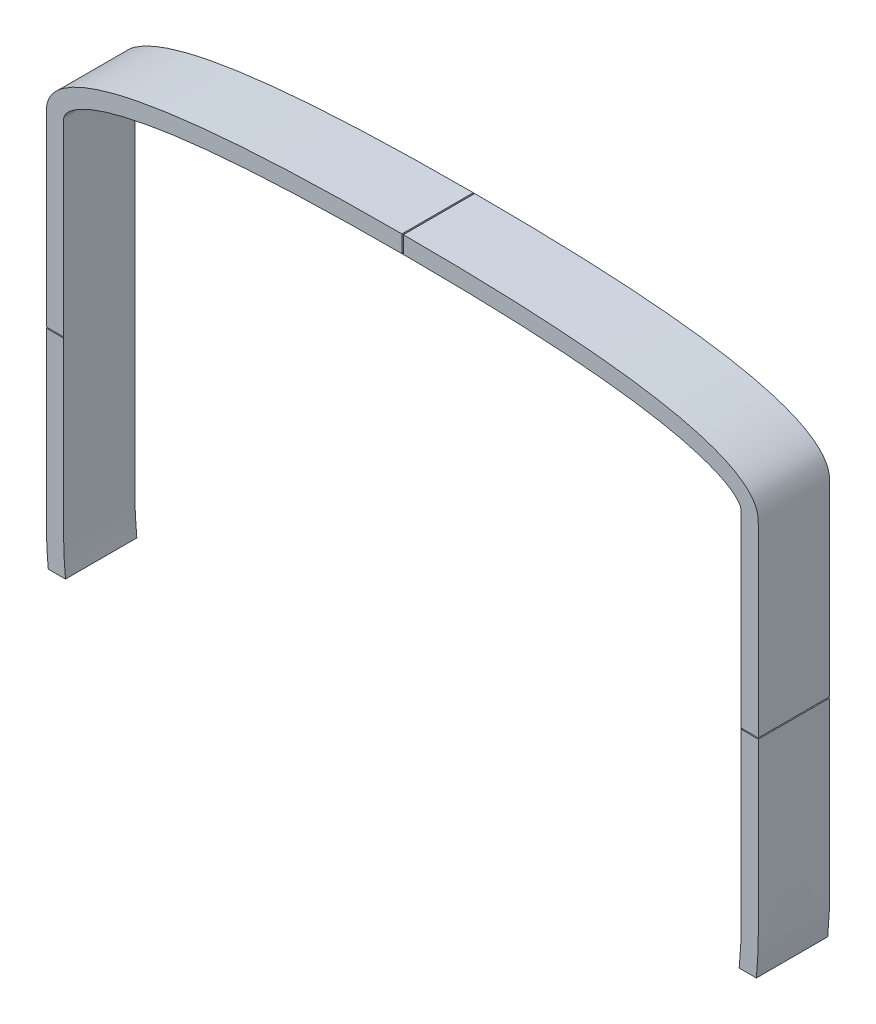
SolidWorks part; units mm, degrees
ref_plane "Front Plane" through (0, 0, 0) normal (0, 0, 1) x (1, 0, 0)
ref_plane "Top Plane" through (0, 0, 0) normal (0, 1, 0) x (1, 0, 0)
ref_plane "Right Plane" through (0, 0, 0) normal (1, 0, 0) x (0, 0, -1)
sketch "Sketch1" plane through (0, 0, 0) normal (0, 0, 1) x (1, 0, 0)
  line L0 (-100.01, 47.0605) -> (-95.145, 47.0605) construction
  line L1 (-95.145, 47.0605) -> (-95.145, 47.3605) construction
  line L2 (-95.145, 47.3605) -> (-100.01, 47.3605) construction
  line L3 (0.3, -80.0112) -> (0.3, -75.1462) construction
  line L4 (0.3, -75.1462) -> (-0.1, -75.1462) construction
  line L5 (-0.1, -75.1462) -> (-0.1, -80.0113) construction
  line L6 (100.01, 47.0605) -> (95.145, 47.0605) construction
  line L7 (95.145, 47.0605) -> (95.145, 47.3605) construction
  line L8 (95.145, 47.3605) -> (100.01, 47.3605) construction
  line L9 (-0.1, 120.0108) -> (-0.1, 115.1456) construction
  line L10 (-0.1, 115.1456) -> (0.3, 115.1456) construction
  line L11 (0.3, 115.1456) -> (0.3, 120) construction
  line L12 (-100.01, 47.0605) -> (-95.145, 47.0605)
  line L13 (-95.145, 47.0605) -> (-95.145, 47.3605)
  line L14 (-95.145, 47.3605) -> (-100.01, 47.3605)
  line L15 (0.3, -80.0112) -> (0.3, -75.1462)
  line L16 (0.3, -75.1462) -> (-0.1, -75.1462)
  line L17 (-0.1, -75.1462) -> (-0.1, -80.0113)
  line L18 (100.01, 47.0605) -> (95.145, 47.0605)
  line L19 (95.145, 47.0605) -> (95.145, 47.3605)
  line L20 (95.145, 47.3605) -> (100.01, 47.3605)
  line L21 (-0.1, 120.0108) -> (-0.1, 115.1456)
  line L22 (-0.1, 115.1456) -> (0.3, 115.1456)
  line L23 (0.3, 115.1456) -> (0.3, 120)
  spline S1 degree 3 poles (99.7997, 99.6773) (99.8036, 99.9509) (99.7918, 100.4046) (99.7567, 100.8662) (99.681, 101.3713) (99.4748, 102.3026) (98.9784, 103.5224) (98.2111, 104.7064) (97.4509, 105.6067) (96.7168, 106.336) (95.7397, 107.1776) (94.5505, 108.0336) (93.1451, 108.8913) (91.7553, 109.627) (90.3759, 110.2763) (88.5549, 111.0479) (86.2863, 111.8842) (83.5821, 112.7336) (80.8863, 113.4732) (77.3062, 114.3386) (72.8372, 115.247) (67.4911, 116.1276) (62.1537, 116.8577) (55.0502, 117.6648) (46.1798, 118.4308) (35.5554, 119.0568) (24.9443, 119.4728) (10.8109, 119.7907) (-3.2959, 119.8408) (-17.4186, 119.6586) (-28.0207, 119.3706) (-38.6348, 118.9) (-49.264, 118.1957) (-58.1353, 117.3502) (-65.2481, 116.4514) (-70.5879, 115.6377) (-75.9423, 114.6434) (-80.4143, 113.6143) (-84.0118, 112.6066) (-86.7154, 111.7373) (-88.9907, 110.8755) (-90.8116, 110.0789) (-92.1968, 109.4029) (-93.5848, 108.6377) (-94.773, 107.876) (-95.7176, 107.1784) (-96.45, 106.576) (-97.1862, 105.883) (-97.9288, 105.0629) (-98.5735, 104.1718) (-99.0633, 103.2704) (-99.3935, 102.4897) (-99.6149, 101.7198) (-99.7273, 101.0847) (-99.7694, 100.7104) (-99.7903, 100.4114) (-99.7992, 100.1667) (-99.8002, 99.9845) (-99.7998, 99.869) (-99.7998, 99.7406) (-99.7998, 99.5238) (-99.8, 99.2514) (-99.8003, 98.8108) (-99.8005, 98.2617) (-99.8006, 97.6024) (-99.8006, 96.7238) (-99.8004, 95.626) (-99.8, 94.3096) (-99.7998, 92.994) (-99.7998, 91.2393) (-99.8, 89.0456) (-99.8002, 86.4124) (-99.8002, 83.7794) (-99.8003, 80.2688) (-99.8002, 75.8805) (-99.8, 70.6147) (-99.7999, 65.349) (-99.7999, 60.0833) (-99.7999, 53.0623) (-99.8, 44.2861) (-99.8001, 33.7545) (-99.8005, 23.2232) (-99.7997, 14.4459) (-99.8011, 7.4266) (-99.7969, 3.0338) (-99.8053, -0.466) (-99.7591, -4.1567) (-99.4387, -10.5423) (-98.2942, -19.73) (-95.5017, -30.6179) (-91.0075, -41.0897) (-84.6521, -50.6636) (-76.6002, -58.8628) (-67.303, -65.4359) (-53.8961, -72.1154) (-36.165, -77.1506) (-18.1876, -79.2977) (-3.835, -79.8498) (10.4785, -79.7642) (28.4686, -78.3932) (49.8925, -73.7834) (67.0953, -66.0502) (79.0866, -56.6481) (86.6805, -48.0163) (92.5016, -38.1179) (96.4764, -27.4833) (98.4332, -18.3609) (99.3377, -11.0291) (99.6551, -6.4456) (99.7809, -2.7913) (99.8043, -0.0384) (99.7991, 2.5844) (99.8005, 6.0917) (99.7999, 10.4829) (99.8001, 17.5023) (99.8, 26.2794) (99.8, 36.8107) (99.8, 47.3423) (99.8, 56.1185) (99.8, 63.1396) (99.8, 68.4053) (99.8, 73.6711) (99.8, 78.9369) (99.8, 83.325) (99.8, 86.8355) (99.8, 89.4684) (99.8, 91.6625) (99.8, 93.4178) (99.8, 94.7342) (99.8, 95.8313) (99.8, 96.7088) (99.8, 97.3675) (99.8, 98.0238) (99.8, 98.5785) (99.8, 99.0062) (99.8001, 99.2955) (99.7997, 99.5144) (99.7997, 99.6773) (99.8036, 99.9509) (99.7918, 100.4046) knots -0.000977 -0.000732 -0.000488 0 0.000244 0.000488 0.000732 0.000977 0.001953 0.00293 0.003906 0.004883 0.005859 0.007812 0.009766 0.011719 0.013672 0.015625 0.019531 0.023438 0.027344 0.03125 0.039062 0.046875 0.054688 0.0625 0.078125 0.09375 0.109375 0.125 0.15625 0.171875 0.1875 0.203125 0.21875 0.234375 0.242188 0.25 0.257812 0.265625 0.269531 0.273438 0.277344 0.279297 0.28125 0.283203 0.285156 0.286133 0.287109 0.288086 0.289062 0.290039 0.290527 0.291016 0.291504 0.291748 0.291992 0.292114 0.292236 0.292358 0.29248 0.292725 0.292969 0.293457 0.293945 0.294922 0.295898 0.296875 0.298828 0.300781 0.302734 0.304688 0.308594 0.3125 0.316406 0.320312 0.328125 0.335938 0.34375 0.351562 0.359375 0.375 0.390625 0.40625 0.421875 0.429688 0.4375 0.441406 0.445312 0.453125 0.46875 0.484375 0.5 0.515625 0.53125 0.546875 0.5625 0.59375 0.625 0.640625 0.65625 0.6875 0.71875 0.75 0.765625 0.78125 0.796875 0.8125 0.828125 0.835938 0.84375 0.847656 0.851562 0.855469 0.859375 0.867188 0.875 0.890625 0.90625 0.921875 0.9375 0.945312 0.953125 0.960938 0.96875 0.976562 0.980469 0.984375 0.988281 0.990234 0.992188 0.994141 0.995117 0.996094 0.99707 0.998047 0.998535 0.999023 0.999268 0.999512 1 1.000244 1.000488 1.000732 only from (99.7993, 100.0793) to (99.7993, 100.0793)
  spline S2 degree 3 poles (99.7997, 99.6773) (99.8036, 99.9509) (99.7918, 100.4046) (99.7567, 100.8662) (99.681, 101.3713) (99.4748, 102.3026) (98.9784, 103.5224) (98.2111, 104.7064) (97.4509, 105.6067) (96.7168, 106.336) (95.7397, 107.1776) (94.5505, 108.0336) (93.1451, 108.8913) (91.7553, 109.627) (90.3759, 110.2763) (88.5549, 111.0479) (86.2863, 111.8842) (83.5821, 112.7336) (80.8863, 113.4732) (77.3062, 114.3386) (72.8372, 115.247) (67.4911, 116.1276) (62.1537, 116.8577) (55.0502, 117.6648) (46.1798, 118.4308) (35.5554, 119.0568) (24.9443, 119.4728) (10.8109, 119.7907) (-3.2959, 119.8408) (-17.4186, 119.6586) (-28.0207, 119.3706) (-38.6348, 118.9) (-49.264, 118.1957) (-58.1353, 117.3502) (-65.2481, 116.4514) (-70.5879, 115.6377) (-75.9423, 114.6434) (-80.4143, 113.6143) (-84.0118, 112.6066) (-86.7154, 111.7373) (-88.9907, 110.8755) (-90.8116, 110.0789) (-92.1968, 109.4029) (-93.5848, 108.6377) (-94.773, 107.876) (-95.7176, 107.1784) (-96.45, 106.576) (-97.1862, 105.883) (-97.9288, 105.0629) (-98.5735, 104.1718) (-99.0633, 103.2704) (-99.3935, 102.4897) (-99.6149, 101.7198) (-99.7273, 101.0847) (-99.7694, 100.7104) (-99.7903, 100.4114) (-99.7992, 100.1667) (-99.8002, 99.9845) (-99.7998, 99.869) (-99.7998, 99.7406) (-99.7998, 99.5238) (-99.8, 99.2514) (-99.8003, 98.8108) (-99.8005, 98.2617) (-99.8006, 97.6024) (-99.8006, 96.7238) (-99.8004, 95.626) (-99.8, 94.3096) (-99.7998, 92.994) (-99.7998, 91.2393) (-99.8, 89.0456) (-99.8002, 86.4124) (-99.8002, 83.7794) (-99.8003, 80.2688) (-99.8002, 75.8805) (-99.8, 70.6147) (-99.7999, 65.349) (-99.7999, 60.0833) (-99.7999, 53.0623) (-99.8, 44.2861) (-99.8001, 33.7545) (-99.8005, 23.2232) (-99.7997, 14.4459) (-99.8011, 7.4266) (-99.7969, 3.0338) (-99.8053, -0.466) (-99.7591, -4.1567) (-99.4387, -10.5423) (-98.2942, -19.73) (-95.5017, -30.6179) (-91.0075, -41.0897) (-84.6521, -50.6636) (-76.6002, -58.8628) (-67.303, -65.4359) (-53.8961, -72.1154) (-36.165, -77.1506) (-18.1876, -79.2977) (-3.835, -79.8498) (10.4785, -79.7642) (28.4686, -78.3932) (49.8925, -73.7834) (67.0953, -66.0502) (79.0866, -56.6481) (86.6805, -48.0163) (92.5016, -38.1179) (96.4764, -27.4833) (98.4332, -18.3609) (99.3377, -11.0291) (99.6551, -6.4456) (99.7809, -2.7913) (99.8043, -0.0384) (99.7991, 2.5844) (99.8005, 6.0917) (99.7999, 10.4829) (99.8001, 17.5023) (99.8, 26.2794) (99.8, 36.8107) (99.8, 47.3423) (99.8, 56.1185) (99.8, 63.1396) (99.8, 68.4053) (99.8, 73.6711) (99.8, 78.9369) (99.8, 83.325) (99.8, 86.8355) (99.8, 89.4684) (99.8, 91.6625) (99.8, 93.4178) (99.8, 94.7342) (99.8, 95.8313) (99.8, 96.7088) (99.8, 97.3675) (99.8, 98.0238) (99.8, 98.5785) (99.8, 99.0062) (99.8001, 99.2955) (99.7997, 99.5144) (99.7997, 99.6773) (99.8036, 99.9509) (99.7918, 100.4046) knots -0.000977 -0.000732 -0.000488 0 0.000244 0.000488 0.000732 0.000977 0.001953 0.00293 0.003906 0.004883 0.005859 0.007812 0.009766 0.011719 0.013672 0.015625 0.019531 0.023438 0.027344 0.03125 0.039062 0.046875 0.054688 0.0625 0.078125 0.09375 0.109375 0.125 0.15625 0.171875 0.1875 0.203125 0.21875 0.234375 0.242188 0.25 0.257812 0.265625 0.269531 0.273438 0.277344 0.279297 0.28125 0.283203 0.285156 0.286133 0.287109 0.288086 0.289062 0.290039 0.290527 0.291016 0.291504 0.291748 0.291992 0.292114 0.292236 0.292358 0.29248 0.292725 0.292969 0.293457 0.293945 0.294922 0.295898 0.296875 0.298828 0.300781 0.302734 0.304688 0.308594 0.3125 0.316406 0.320312 0.328125 0.335938 0.34375 0.351562 0.359375 0.375 0.390625 0.40625 0.421875 0.429688 0.4375 0.441406 0.445312 0.453125 0.46875 0.484375 0.5 0.515625 0.53125 0.546875 0.5625 0.59375 0.625 0.640625 0.65625 0.6875 0.71875 0.75 0.765625 0.78125 0.796875 0.8125 0.828125 0.835938 0.84375 0.847656 0.851562 0.855469 0.859375 0.867188 0.875 0.890625 0.90625 0.921875 0.9375 0.945312 0.953125 0.960938 0.96875 0.976562 0.980469 0.984375 0.988281 0.990234 0.992188 0.994141 0.995117 0.996094 0.99707 0.998047 0.998535 0.999023 0.999268 0.999512 1 1.000244 1.000488 1.000732 only from (99.7993, 100.0793) to (99.7993, 100.0793)
  spline S3 degree 3 poles (94.9991, 99.6498) (95.0033, 99.9945) (94.9886, 100.3305) (94.9285, 100.6507) (94.8294, 100.9604) (94.5623, 101.5544) (93.9794, 102.3192) (93.0263, 103.2069) (91.6762, 104.1962) (89.7643, 105.2891) (86.7225, 106.6551) (82.5543, 108.083) (76.1132, 109.7535) (67.4455, 111.3546) (54.2601, 113.0179) (36.6733, 114.3033) (21.0967, 114.796) (10.1079, 114.9512) (4.9035, 114.9925) (-0.3225, 115.0048) (-7.3652, 114.9836) (-16.0311, 114.8829) (-26.9636, 114.6065) (-37.956, 114.1366) (-48.8577, 113.4115) (-58.667, 112.4743) (-66.6295, 111.4261) (-72.9317, 110.3437) (-78.1678, 109.2363) (-83.1304, 107.9121) (-87.3123, 106.426) (-90.3426, 104.9929) (-92.2115, 103.8445) (-93.3583, 102.913) (-93.9767, 102.2848) (-94.5313, 101.602) (-94.8966, 100.9077) (-94.9869, 100.3092) (-95.0003, 100.0907) (-94.9996, 99.7607) (-95.0013, 97.7241) (-94.9995, 93.9804) (-95.0006, 84.2276) (-94.9997, 68.373) (-95, 40.1872) (-95.0005, 17.4761) (-94.9999, 2.1967) (-95.0002, 0.4352) (-94.9982, -2.3323) (-94.8101, -8.1993) (-93.8713, -17.1447) (-91.4322, -27.5753) (-87.8502, -36.4563) (-83.6838, -43.555) (-79.3185, -49.2124) (-73.5088, -55.0355) (-65.8142, -60.7188) (-56.8099, -65.3701) (-47.6395, -68.7951) (-37.8771, -71.4534) (-26.8877, -73.4301) (-15.4181, -74.5813) (-6.1485, -74.9679) (0.8919, -75.0173) (7.9604, -74.9151) (16.7848, -74.4683) (27.3133, -73.3359) (37.741, -71.4746) (51.3819, -67.8285) (64.4819, -61.969) (74.2954, -54.3104) (79.226, -49.2152) (83.6031, -43.7463) (88.1341, -36.0845) (91.8283, -26.2136) (94.0819, -15.7449) (94.8156, -7.8256) (94.9715, -2.8766) (94.9968, -1.1263) (95.0018, 0.6243) (94.9994, 2.8316) (95.0003, 6.3331) (94.9999, 10.7101) (95, 14.3284) (95, 16.3126) (95, 16.6627) (95, 17.0129) (95, 17.3631) (95, 17.7132) (95, 18.0634) (95, 18.4135) (95, 18.7637) (95, 19.1138) (95, 19.464) (95, 19.8142) (95, 20.1643) (95, 20.5145) (95, 20.8646) (95, 21.2148) (95, 21.5649) (95, 21.9151) (95, 22.2652) (95, 22.6154) (95, 22.9656) (95, 23.3157) (95, 23.6659) (95, 24.016) (95, 24.3662) (95, 24.7163) (95, 25.0665) (95, 25.4167) (95, 25.7668) (95, 26.117) (95, 26.4671) (95, 26.8173) (95, 27.1674) (95, 27.5176) (95, 27.8678) (95, 28.2179) (95, 28.5681) (95, 28.9182) (95, 29.2684) (95, 29.6185) (95, 29.9687) (95, 30.3188) (95, 30.669) (95, 31.0192) (95, 31.3693) (95, 31.7195) (95, 32.0696) (95, 32.4198) (95, 32.7699) (95, 33.1201) (95, 33.4703) (95, 33.8204) (95, 34.1706) (95, 34.5207) (95, 34.8709) (95, 35.221) (95, 35.5712) (95, 35.9213) (95, 36.2715) (95, 36.6217) (95, 36.9718) (95, 37.322) (95, 37.6721) (95, 38.0223) (95, 38.3724) (95, 38.7226) (95, 39.0728) (95, 39.4229) (95, 39.7731) (95, 40.1232) (95, 40.4734) (95, 40.8235) (95, 41.1737) (95, 41.5239) (95, 41.874) (95, 42.2242) (95, 42.5743) (95, 42.9245) (95, 43.2746) (95, 43.6248) (95, 43.9749) (95, 44.3251) (95, 44.6753) (95, 45.0254) (95, 45.3756) (95, 45.7257) (95, 46.0759) (95, 46.426) (95, 46.7762) (95, 47.1264) (95, 47.4765) (95, 47.8267) (95, 48.1768) (95, 48.527) (95, 48.8771) (95, 49.2273) (95, 49.5774) (95, 49.9276) (95, 50.2778) (95, 50.6279) (95, 50.9781) (95, 51.3282) (95, 51.6784) (95, 52.0285) (95, 52.3787) (95, 52.7289) (95, 53.079) (95, 53.4292) (95, 53.7793) (95, 54.1295) (95, 54.4796) (95, 54.8298) (95, 55.18) (95, 55.5301) (95, 55.8803) (95, 56.2304) (95, 56.5806) (95, 56.9307) (95, 57.2809) (95, 57.631) (95, 57.9812) (95, 58.3314) (95, 58.6815) (95, 59.0317) (95, 59.3818) (95, 59.732) (95, 60.0821) (95, 60.4323) (95, 60.7825) (95, 61.1326) (95, 61.4828) (95, 61.8329) (95, 62.1831) (95, 62.5332) (95, 62.8834) (95, 63.2336) (95, 63.5837) (95, 63.9339) (95, 64.284) (95, 64.6342) (95, 64.9843) (95, 65.3345) (95, 65.6846) (95, 66.0348) (95, 66.385) (95, 66.7351) (95, 67.0853) (95, 67.4354) (95, 67.7856) (95, 68.1357) (95, 68.4859) (95, 68.8361) (95, 69.1862) (95, 69.5364) (95, 69.8865) (95, 70.2367) (95, 70.5868) (95, 70.937) (95, 71.2871) (95, 71.6373) (95, 71.9875) (95, 72.3376) (95, 72.6878) (95, 73.0379) (95, 73.3881) (95, 73.7382) (95, 74.0884) (95, 74.4386) (95, 74.7887) (95, 75.1389) (95, 75.489) (95, 75.8392) (95, 76.1893) (95, 76.5395) (95, 76.8897) (95, 77.2398) (95, 77.59) (95, 77.9401) (95, 78.2903) (95, 78.6404) (95, 78.9906) (95, 79.3407) (95, 79.6909) (95, 80.0411) (95, 80.3912) (95, 80.7414) (95, 81.0915) (95, 81.4417) (95, 81.7918) (95, 82.142) (95, 82.4922) (95, 82.8423) (95, 83.1925) (95, 83.5426) (95, 83.8928) (95, 84.2429) (95, 84.5931) (95, 84.9432) (95, 85.2934) (95, 85.6436) (95, 85.9937) (95, 86.3439) (95, 86.694) (95, 87.0442) (95, 87.3943) (95, 87.7445) (95, 88.0947) (95, 88.4448) (95, 88.795) (95, 89.1451) (95, 89.4953) (95, 89.8454) (95, 90.1956) (95, 90.5458) (95, 90.8959) (95, 91.2461) (95, 91.5962) (95, 91.9464) (95, 92.2965) (95, 92.6467) (95, 92.9968) (95, 93.347) (95, 93.6972) (95, 94.0473) (95, 94.3975) (95, 94.7476) (95, 95.0978) (95, 95.4479) (95, 95.7981) (95, 96.1483) (95, 96.4984) (95, 96.8486) (95, 97.1987) (95, 97.5489) (95, 97.899) (95, 98.2492) (95, 98.5994) (94.9999, 98.9495) (95.0002, 99.2997) (94.9991, 99.6498) (95.0033, 99.9945) (94.9886, 100.3305) knots -0.001559 -0.001039 -0.00052 0 0.000495 0.000974 0.001446 0.001939 0.003867 0.005664 0.00773 0.011301 0.015445 0.022555 0.030881 0.045044 0.061752 0.090013 0.123492 0.131103 0.138928 0.146657 0.154364 0.170275 0.185229 0.203037 0.219242 0.233854 0.246889 0.254977 0.26231 0.270704 0.277822 0.282028 0.285605 0.287554 0.288589 0.28952 0.291476 0.291962 0.292206 0.29245 0.293431 0.301271 0.309112 0.33684 0.371839 0.434565 0.437925 0.439846 0.442406 0.450243 0.465965 0.482358 0.497762 0.508388 0.518904 0.52948 0.544908 0.56127 0.574423 0.588416 0.606248 0.624055 0.639683 0.647525 0.655389 0.671146 0.686832 0.702495 0.718232 0.749659 0.765474 0.773344 0.781173 0.796611 0.812727 0.82787 0.84415 0.848045 0.849909 0.851941 0.855837 0.859734 0.867526 0.875319 0.875838 0.876358 0.876877 0.877397 0.877916 0.878436 0.878955 0.879475 0.879994 0.880514 0.881033 0.881553 0.882072 0.882592 0.883111 0.883631 0.88415 0.88467 0.885189 0.885709 0.886228 0.886748 0.887267 0.887787 0.888306 0.888826 0.889345 0.889865 0.890384 0.890904 0.891423 0.891943 0.892462 0.892982 0.893501 0.894021 0.89454 0.89506 0.895579 0.896099 0.896618 0.897138 0.897657 0.898177 0.898696 0.899216 0.899735 0.900255 0.900774 0.901294 0.901813 0.902333 0.902852 0.903372 0.903891 0.904411 0.90493 0.90545 0.90597 0.906489 0.907009 0.907528 0.908048 0.908567 0.909087 0.909606 0.910126 0.910645 0.911165 0.911684 0.912204 0.912723 0.913243 0.913762 0.914282 0.914801 0.915321 0.91584 0.91636 0.916879 0.917399 0.917918 0.918438 0.918957 0.919477 0.919996 0.920516 0.921035 0.921555 0.922074 0.922594 0.923113 0.923633 0.924152 0.924672 0.925191 0.925711 0.92623 0.92675 0.927269 0.927789 0.928308 0.928828 0.929347 0.929867 0.930386 0.930906 0.931425 0.931945 0.932464 0.932984 0.933503 0.934023 0.934542 0.935062 0.935581 0.936101 0.93662 0.93714 0.937659 0.938179 0.938698 0.939218 0.939737 0.940257 0.940776 0.941296 0.941815 0.942335 0.942854 0.943374 0.943893 0.944413 0.944932 0.945452 0.945971 0.946491 0.94701 0.94753 0.948049 0.948569 0.949088 0.949608 0.950127 0.950647 0.951166 0.951686 0.952205 0.952725 0.953245 0.953764 0.954284 0.954803 0.955323 0.955842 0.956362 0.956881 0.957401 0.95792 0.95844 0.958959 0.959479 0.959998 0.960518 0.961037 0.961557 0.962076 0.962596 0.963115 0.963635 0.964154 0.964674 0.965193 0.965713 0.966232 0.966752 0.967271 0.967791 0.96831 0.96883 0.969349 0.969869 0.970388 0.970908 0.971427 0.971947 0.972466 0.972986 0.973505 0.974025 0.974544 0.975064 0.975583 0.976103 0.976622 0.977142 0.977661 0.978181 0.9787 0.97922 0.979739 0.980259 0.980778 0.981298 0.981817 0.982337 0.982856 0.983376 0.983895 0.984415 0.984934 0.985454 0.985973 0.986493 0.987012 0.987532 0.988051 0.988571 0.98909 0.98961 0.990129 0.990649 0.991168 0.991688 0.992207 0.992727 0.993246 0.993766 0.994285 0.994805 0.995324 0.995844 0.996363 0.996883 0.997402 0.997922 0.998441 0.998961 0.99948 1 1.000495 1.000974 1.001446 only from (95, 100) to (95, 100)
  spline S4 degree 3 poles (94.9991, 99.6498) (95.0033, 99.9945) (94.9886, 100.3305) (94.9285, 100.6507) (94.8294, 100.9604) (94.5623, 101.5544) (93.9794, 102.3192) (93.0263, 103.2069) (91.6762, 104.1962) (89.7643, 105.2891) (86.7225, 106.6551) (82.5543, 108.083) (76.1132, 109.7535) (67.4455, 111.3546) (54.2601, 113.0179) (36.6733, 114.3033) (21.0967, 114.796) (10.1079, 114.9512) (4.9035, 114.9925) (-0.3225, 115.0048) (-7.3652, 114.9836) (-16.0311, 114.8829) (-26.9636, 114.6065) (-37.956, 114.1366) (-48.8577, 113.4115) (-58.667, 112.4743) (-66.6295, 111.4261) (-72.9317, 110.3437) (-78.1678, 109.2363) (-83.1304, 107.9121) (-87.3123, 106.426) (-90.3426, 104.9929) (-92.2115, 103.8445) (-93.3583, 102.913) (-93.9767, 102.2848) (-94.5313, 101.602) (-94.8966, 100.9077) (-94.9869, 100.3092) (-95.0003, 100.0907) (-94.9996, 99.7607) (-95.0013, 97.7241) (-94.9995, 93.9804) (-95.0006, 84.2276) (-94.9997, 68.373) (-95, 40.1872) (-95.0005, 17.4761) (-94.9999, 2.1967) (-95.0002, 0.4352) (-94.9982, -2.3323) (-94.8101, -8.1993) (-93.8713, -17.1447) (-91.4322, -27.5753) (-87.8502, -36.4563) (-83.6838, -43.555) (-79.3185, -49.2124) (-73.5088, -55.0355) (-65.8142, -60.7188) (-56.8099, -65.3701) (-47.6395, -68.7951) (-37.8771, -71.4534) (-26.8877, -73.4301) (-15.4181, -74.5813) (-6.1485, -74.9679) (0.8919, -75.0173) (7.9604, -74.9151) (16.7848, -74.4683) (27.3133, -73.3359) (37.741, -71.4746) (51.3819, -67.8285) (64.4819, -61.969) (74.2954, -54.3104) (79.226, -49.2152) (83.6031, -43.7463) (88.1341, -36.0845) (91.8283, -26.2136) (94.0819, -15.7449) (94.8156, -7.8256) (94.9715, -2.8766) (94.9968, -1.1263) (95.0018, 0.6243) (94.9994, 2.8316) (95.0003, 6.3331) (94.9999, 10.7101) (95, 14.3284) (95, 16.3126) (95, 16.6627) (95, 17.0129) (95, 17.3631) (95, 17.7132) (95, 18.0634) (95, 18.4135) (95, 18.7637) (95, 19.1138) (95, 19.464) (95, 19.8142) (95, 20.1643) (95, 20.5145) (95, 20.8646) (95, 21.2148) (95, 21.5649) (95, 21.9151) (95, 22.2652) (95, 22.6154) (95, 22.9656) (95, 23.3157) (95, 23.6659) (95, 24.016) (95, 24.3662) (95, 24.7163) (95, 25.0665) (95, 25.4167) (95, 25.7668) (95, 26.117) (95, 26.4671) (95, 26.8173) (95, 27.1674) (95, 27.5176) (95, 27.8678) (95, 28.2179) (95, 28.5681) (95, 28.9182) (95, 29.2684) (95, 29.6185) (95, 29.9687) (95, 30.3188) (95, 30.669) (95, 31.0192) (95, 31.3693) (95, 31.7195) (95, 32.0696) (95, 32.4198) (95, 32.7699) (95, 33.1201) (95, 33.4703) (95, 33.8204) (95, 34.1706) (95, 34.5207) (95, 34.8709) (95, 35.221) (95, 35.5712) (95, 35.9213) (95, 36.2715) (95, 36.6217) (95, 36.9718) (95, 37.322) (95, 37.6721) (95, 38.0223) (95, 38.3724) (95, 38.7226) (95, 39.0728) (95, 39.4229) (95, 39.7731) (95, 40.1232) (95, 40.4734) (95, 40.8235) (95, 41.1737) (95, 41.5239) (95, 41.874) (95, 42.2242) (95, 42.5743) (95, 42.9245) (95, 43.2746) (95, 43.6248) (95, 43.9749) (95, 44.3251) (95, 44.6753) (95, 45.0254) (95, 45.3756) (95, 45.7257) (95, 46.0759) (95, 46.426) (95, 46.7762) (95, 47.1264) (95, 47.4765) (95, 47.8267) (95, 48.1768) (95, 48.527) (95, 48.8771) (95, 49.2273) (95, 49.5774) (95, 49.9276) (95, 50.2778) (95, 50.6279) (95, 50.9781) (95, 51.3282) (95, 51.6784) (95, 52.0285) (95, 52.3787) (95, 52.7289) (95, 53.079) (95, 53.4292) (95, 53.7793) (95, 54.1295) (95, 54.4796) (95, 54.8298) (95, 55.18) (95, 55.5301) (95, 55.8803) (95, 56.2304) (95, 56.5806) (95, 56.9307) (95, 57.2809) (95, 57.631) (95, 57.9812) (95, 58.3314) (95, 58.6815) (95, 59.0317) (95, 59.3818) (95, 59.732) (95, 60.0821) (95, 60.4323) (95, 60.7825) (95, 61.1326) (95, 61.4828) (95, 61.8329) (95, 62.1831) (95, 62.5332) (95, 62.8834) (95, 63.2336) (95, 63.5837) (95, 63.9339) (95, 64.284) (95, 64.6342) (95, 64.9843) (95, 65.3345) (95, 65.6846) (95, 66.0348) (95, 66.385) (95, 66.7351) (95, 67.0853) (95, 67.4354) (95, 67.7856) (95, 68.1357) (95, 68.4859) (95, 68.8361) (95, 69.1862) (95, 69.5364) (95, 69.8865) (95, 70.2367) (95, 70.5868) (95, 70.937) (95, 71.2871) (95, 71.6373) (95, 71.9875) (95, 72.3376) (95, 72.6878) (95, 73.0379) (95, 73.3881) (95, 73.7382) (95, 74.0884) (95, 74.4386) (95, 74.7887) (95, 75.1389) (95, 75.489) (95, 75.8392) (95, 76.1893) (95, 76.5395) (95, 76.8897) (95, 77.2398) (95, 77.59) (95, 77.9401) (95, 78.2903) (95, 78.6404) (95, 78.9906) (95, 79.3407) (95, 79.6909) (95, 80.0411) (95, 80.3912) (95, 80.7414) (95, 81.0915) (95, 81.4417) (95, 81.7918) (95, 82.142) (95, 82.4922) (95, 82.8423) (95, 83.1925) (95, 83.5426) (95, 83.8928) (95, 84.2429) (95, 84.5931) (95, 84.9432) (95, 85.2934) (95, 85.6436) (95, 85.9937) (95, 86.3439) (95, 86.694) (95, 87.0442) (95, 87.3943) (95, 87.7445) (95, 88.0947) (95, 88.4448) (95, 88.795) (95, 89.1451) (95, 89.4953) (95, 89.8454) (95, 90.1956) (95, 90.5458) (95, 90.8959) (95, 91.2461) (95, 91.5962) (95, 91.9464) (95, 92.2965) (95, 92.6467) (95, 92.9968) (95, 93.347) (95, 93.6972) (95, 94.0473) (95, 94.3975) (95, 94.7476) (95, 95.0978) (95, 95.4479) (95, 95.7981) (95, 96.1483) (95, 96.4984) (95, 96.8486) (95, 97.1987) (95, 97.5489) (95, 97.899) (95, 98.2492) (95, 98.5994) (94.9999, 98.9495) (95.0002, 99.2997) (94.9991, 99.6498) (95.0033, 99.9945) (94.9886, 100.3305) knots -0.001559 -0.001039 -0.00052 0 0.000495 0.000974 0.001446 0.001939 0.003867 0.005664 0.00773 0.011301 0.015445 0.022555 0.030881 0.045044 0.061752 0.090013 0.123492 0.131103 0.138928 0.146657 0.154364 0.170275 0.185229 0.203037 0.219242 0.233854 0.246889 0.254977 0.26231 0.270704 0.277822 0.282028 0.285605 0.287554 0.288589 0.28952 0.291476 0.291962 0.292206 0.29245 0.293431 0.301271 0.309112 0.33684 0.371839 0.434565 0.437925 0.439846 0.442406 0.450243 0.465965 0.482358 0.497762 0.508388 0.518904 0.52948 0.544908 0.56127 0.574423 0.588416 0.606248 0.624055 0.639683 0.647525 0.655389 0.671146 0.686832 0.702495 0.718232 0.749659 0.765474 0.773344 0.781173 0.796611 0.812727 0.82787 0.84415 0.848045 0.849909 0.851941 0.855837 0.859734 0.867526 0.875319 0.875838 0.876358 0.876877 0.877397 0.877916 0.878436 0.878955 0.879475 0.879994 0.880514 0.881033 0.881553 0.882072 0.882592 0.883111 0.883631 0.88415 0.88467 0.885189 0.885709 0.886228 0.886748 0.887267 0.887787 0.888306 0.888826 0.889345 0.889865 0.890384 0.890904 0.891423 0.891943 0.892462 0.892982 0.893501 0.894021 0.89454 0.89506 0.895579 0.896099 0.896618 0.897138 0.897657 0.898177 0.898696 0.899216 0.899735 0.900255 0.900774 0.901294 0.901813 0.902333 0.902852 0.903372 0.903891 0.904411 0.90493 0.90545 0.90597 0.906489 0.907009 0.907528 0.908048 0.908567 0.909087 0.909606 0.910126 0.910645 0.911165 0.911684 0.912204 0.912723 0.913243 0.913762 0.914282 0.914801 0.915321 0.91584 0.91636 0.916879 0.917399 0.917918 0.918438 0.918957 0.919477 0.919996 0.920516 0.921035 0.921555 0.922074 0.922594 0.923113 0.923633 0.924152 0.924672 0.925191 0.925711 0.92623 0.92675 0.927269 0.927789 0.928308 0.928828 0.929347 0.929867 0.930386 0.930906 0.931425 0.931945 0.932464 0.932984 0.933503 0.934023 0.934542 0.935062 0.935581 0.936101 0.93662 0.93714 0.937659 0.938179 0.938698 0.939218 0.939737 0.940257 0.940776 0.941296 0.941815 0.942335 0.942854 0.943374 0.943893 0.944413 0.944932 0.945452 0.945971 0.946491 0.94701 0.94753 0.948049 0.948569 0.949088 0.949608 0.950127 0.950647 0.951166 0.951686 0.952205 0.952725 0.953245 0.953764 0.954284 0.954803 0.955323 0.955842 0.956362 0.956881 0.957401 0.95792 0.95844 0.958959 0.959479 0.959998 0.960518 0.961037 0.961557 0.962076 0.962596 0.963115 0.963635 0.964154 0.964674 0.965193 0.965713 0.966232 0.966752 0.967271 0.967791 0.96831 0.96883 0.969349 0.969869 0.970388 0.970908 0.971427 0.971947 0.972466 0.972986 0.973505 0.974025 0.974544 0.975064 0.975583 0.976103 0.976622 0.977142 0.977661 0.978181 0.9787 0.97922 0.979739 0.980259 0.980778 0.981298 0.981817 0.982337 0.982856 0.983376 0.983895 0.984415 0.984934 0.985454 0.985973 0.986493 0.987012 0.987532 0.988051 0.988571 0.98909 0.98961 0.990129 0.990649 0.991168 0.991688 0.992207 0.992727 0.993246 0.993766 0.994285 0.994805 0.995324 0.995844 0.996363 0.996883 0.997402 0.997922 0.998441 0.998961 0.99948 1 1.000495 1.000974 1.001446 only from (95, 100) to (95, 100)
  dimension "D1" = 0
  dimension "D2" = 0
extrude "Boss-Extrude1" add sketch "Sketch1" along normal mid plane 20 contours L21 S2 L14 L13 L12 L17 L16 L15 L18 L19 L20 L23 L22 S4 region at (-97.4725, 49.8833, 0)
sketch "Sketch2" plane through (0, 0, 10) normal (0, 0, 1) x (1, 0, 0)
  line L0 (-125.1, -11.198) -> (-125.1, -86.198)
  line L1 (-125.1, -11.198) -> (124.9, -11.198)
  line L2 (-125.1, -11.198) -> (-125.1, 119.802) construction
  line L3 (-125.1, 119.802) -> (124.9, 119.802) construction
  line L4 (124.9, -11.198) -> (124.9, 119.802) construction
  line L5 (-125.1, -86.198) -> (124.9, -86.198)
  line L6 (124.9, -86.198) -> (124.9, -11.198)
  dimension "D1" = 250
  dimension "D2" = 131
  dimension "D3" = 75
extrude "Cut-Extrude1" cut sketch "Sketch2" against normal through all
